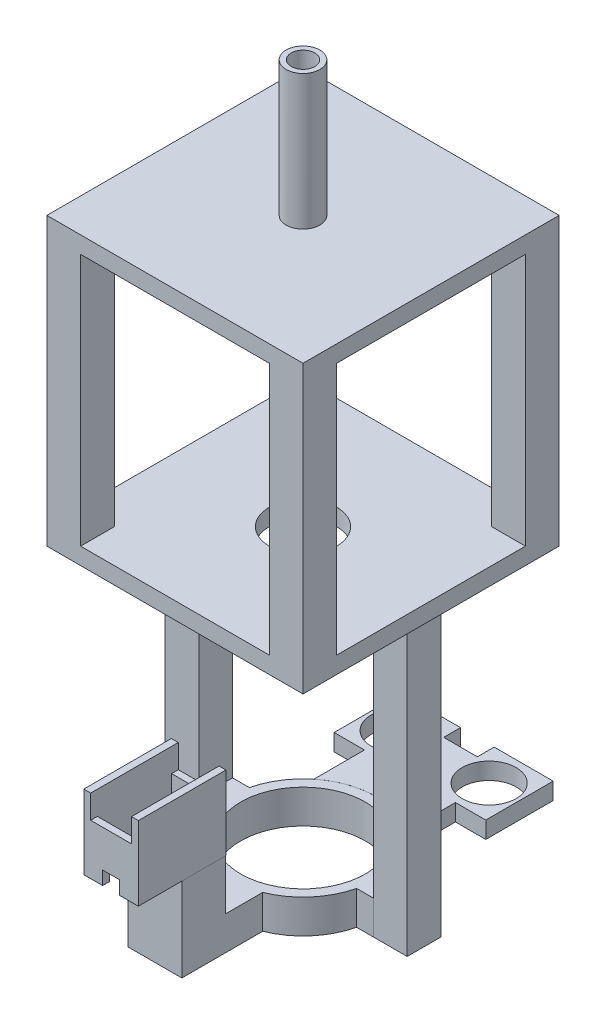
SolidWorks part; units mm, degrees
ref_plane "Front Plane" through (0, 0, 0) normal (0, 0, 1) x (1, 0, 0)
ref_plane "Top Plane" through (0, 0, 0) normal (0, 1, 0) x (1, 0, 0)
ref_plane "Right Plane" through (0, 0, 0) normal (1, 0, 0) x (0, 0, -1)
sketch "Sketch2" plane through (0, 0, 0) normal (0, 1, 0) x (1, 0, 0)
  line L0 (0, 18.5) -> (0, -18.5) construction
  line L1 (-18.5, 0) -> (18.5, 0) construction
  line L2 (0, -5) -> (0, 5) construction
  line L3 (-20.9105, 5) -> (-35.9105, 5)
  line L4 (-35.9105, 5) -> (-35.9105, -5)
  line L5 (-35.9105, -5) -> (-20.9105, -5)
  line L6 (35.9105, -5) -> (20.9105, -5)
  line L7 (35.9105, 5) -> (35.9105, -5)
  line L8 (20.9105, 5) -> (35.9105, 5)
  line L9 (0, 31.7332) -> (22.5, 31.7332)
  line L10 (22.5, 31.7332) -> (22.5, 51.7332)
  line L11 (22.5, 51.7332) -> (5, 51.7332)
  line L12 (-22.5, 51.7332) -> (-22.5, 31.7332)
  line L13 (-22.5, 31.7332) -> (0, 31.7332)
  line L14 (22.5, 41.7332) -> (21.5, 41.7332) construction
  line L20 (-5, 51.7332) -> (-22.5, 51.7332)
  line L21 (0, 46.7332) -> (0, 31.7332) construction
  line L22 (-5, 51.7332) -> (-5, 46.7332)
  line L23 (-5, 46.7332) -> (5, 46.7332)
  line L24 (5, 46.7332) -> (5, 51.7332)
  line L25 (13.5, 49.7332) -> (13.5, 51.7332) construction
  line L26 (13.5, 33.7332) -> (13.5, 31.7332) construction
  line L27 (-13.5, 41.7332) -> (13.5, 41.7332) construction
  line L28 (-13.5, 16.7332) -> (-13.5, 31.7332)
  line L29 (13.5, 31.7332) -> (13.5, 16.7332)
  line L30 (-8, -21.5) -> (8, -21.5) construction
  line L31 (-8, -19.9562) -> (-8, -43.9562)
  line L32 (-8, -43.9562) -> (8, -43.9562)
  line L33 (8, -43.9562) -> (8, -19.9562)
  line L34 (-20.9105, 5) -> (-25.9105, 5) construction
  line L35 (-5.5, -21.5) -> (5.5, -21.5) construction
  line L36 (-25.9105, 5) -> (-25.9105, -5)
  line L37 (25.9105, 5) -> (25.9105, -5)
  circle A0 centre (0, 0) radius 18.5
  circle A1 centre (0, 0) radius 21.5
  circle A2 centre (13.5, 41.7332) radius 8
  circle A3 centre (-13.5, 41.7332) radius 8
  point P9 (0, 0)
  point P45 (0, -21.5)
  point P54 (0, -21.5)
  dimension "D1" = 37
  dimension "D2" = 5
  dimension "D4" = 43
  dimension "D8" = 1
  dimension "D9" = 16
  dimension "D3" = 10
  dimension "D5" = 5
  dimension "D6" = 20
  dimension "D7" = 45
  dimension "D10" = 17.5
  dimension "D11" = 15
  dimension "D12" = 27
  dimension "D13" = 15
  dimension "D14" = 16
  dimension "D15" = 24
  dimension "D16" = 5
extrude "Connector sleeve" add sketch "Sketch2" along normal blind 5 and the other way blind 5 contours A1 A0 | A1 A0 | A1 A0 | A1 A0 region at (-17.6638, 0, -11.1562)
ref_plane "Plane2" through (0, 30, 0) normal (0, 1, 0) x (1, 0, 0)
extrude "Sensor holder" add sketch "Sketch2<10>" along normal blind 5 separate body contours L24 L23 L22 L20 L12 L13 L9 L10 L11 A2 A3 | A1 L29 L9 L13 L28 region at (0, 0, -25.7784) region at (0, 0, -40.8959)
sketch "Sketch2<10>" plane through (0, 0, 0) normal (0, 1, 0) x (1, 0, 0) same geometry as "Sketch2"
extrude "Arms" add sketch "Sketch2<18>" along normal blind 85 from offset 5 contours L36 L3 L4 L5 | L8 L37 L6 L7 region at (-30.9105, 0, 0) region at (30.9105, 0, 0) offset against normal yes
sketch "Sketch2<18>" plane through (0, 0, 0) normal (0, 1, 0) x (1, 0, 0) same geometry as "Sketch2"
extrude "Arms2" add sketch "Sketch2<22>" along normal blind 10 from offset 5 contours A1 L3 L4 L5 | A1 L6 L7 L8 | A1 L3 L36 L5 | A1 L6 L37 L8 region at (-23.6042, 0, 0) region at (-30.9105, 0, 0) region at (23.6042, 0, 0) region at (30.9105, 0, 0) offset against normal yes
sketch "Sketch2<22>" plane through (0, 0, 0) normal (0, 1, 0) x (1, 0, 0) same geometry as "Sketch2"
extrude "Servoholder" add sketch "Sketch2<21>" along normal blind 10 from offset 5 contours A1 L31 L32 L33 region at (0, 0, 32.4701) offset against normal yes
sketch "Sketch2<21>" plane through (0, 0, 0) normal (0, 1, 0) x (1, 0, 0) same geometry as "Sketch2"
sketch "Sketch31" plane through (0, 5, 0) normal (0, 1, 0) x (1, 0, 0)
  line L0 (-8, -43.9562) -> (-8, -30.9562)
  line L1 (-8, -19.9562) -> (-8, -43.9562) construction
  line L2 (-8, -30.9562) -> (8, -30.9562)
  line L3 (8, -43.9562) -> (8, -19.9562) construction
  line L4 (8, -30.9562) -> (8, -43.9562)
  line L5 (8, -43.9562) -> (-8, -43.9562)
  dimension "D1" = 13
extrude "Servoholder2" add sketch "Sketch31" along normal blind 15
sketch "Sketch33" plane through (0, 20, 0) normal (0, 1, 0) x (1, 0, 0)
  line L0 (0, -30.9562) -> (0, -32.9562) construction
  line L1 (8, -30.9562) -> (-8, -30.9562) construction
  line L2 (-8, -43.9562) -> (8, -43.9562) construction
  line L4 (8, -30.9562) -> (-8, -30.9562) construction
  line L6 (-8.1, -30.9562) -> (-8.1, -56.9562)
  line L7 (-8.1, -56.9562) -> (8.1, -56.9562)
  line L8 (8.1, -56.9562) -> (8.1, -30.9562)
  line L9 (0, -43.9562) -> (6.05, -43.9562) construction
  line L10 (0, -56.9562) -> (0, -54.9562) construction
  line L11 (-6.05, -54.9562) -> (6.05, -54.9562)
  line L12 (6.05, -54.9562) -> (6.05, -32.9562)
  line L13 (6.05, -32.9562) -> (-6.05, -32.9562)
  line L14 (-6.05, -54.9562) -> (-6.05, -32.9562)
  line L15 (-8.1, -30.9562) -> (8.1, -30.9562)
  dimension "D1" = 8.1
  dimension "D2" = 26
  dimension "D3" = 6.05
  dimension "D4" = 2
  dimension "D5" = 2
extrude "Servoholder3" add sketch "Sketch33" along normal blind 22
sketch "Servoholder4" plane through (0, 42, 0) normal (0, 1, 0) x (1, 0, 0)
  line L0 (-6.05, -32.9562) -> (-6.05, -30.9562)
  line L1 (8, -30.9562) -> (-8, -30.9562) construction
  line L2 (-6.05, -30.9562) -> (6.05, -30.9562)
  line L3 (8.1, -30.9562) -> (-8.1, -30.9562) construction
  line L4 (6.05, -30.9562) -> (6.05, -32.9562)
  line L5 (6.05, -32.9562) -> (-6.05, -32.9562)
  line L6 (-6.05, -43.9562) -> (6.05, -43.9562) construction
  line L7 (-6.05, -32.9562) -> (-6.05, -54.9562) construction
  line L8 (6.05, -54.9562) -> (6.05, -32.9562) construction
  line L9 (6.05, -56.9562) -> (6.05, -54.9562)
  line L10 (-6.05, -54.9562) -> (-6.05, -56.9562)
  line L11 (-6.05, -56.9562) -> (6.05, -56.9562)
  line L12 (6.05, -54.9562) -> (-6.05, -54.9562)
extrude "Servogrooves" cut sketch "Servoholder4" against normal blind 7
sketch "Sketch36" plane through (0, 0, 56.9562) normal (0, 0, 1) x (1, 0, 0)
  line L0 (0, 20) -> (0, 24) construction
  line L1 (-8.1, 20) -> (8.1, 20) construction
  line L2 (-2.5, 24) -> (2.5, 24)
  line L3 (-2.5, 24) -> (-2.5, 20)
  line L4 (-6.05, 20) -> (6.05, 20) construction
  line L5 (2.5, 24) -> (2.5, 20)
  line L6 (2.5, 20) -> (-2.5, 20)
  point P8 (0, 24)
  dimension "D1" = 4
  dimension "D2" = 2.5
extrude "Servowiring" cut sketch "Sketch36" against normal blind 2
sketch "Sketch4" plane through (0, 80, 0) normal (0, 1, 0) x (1, 0, 0)
  line L1 (-38, -38) -> (38, -38)
  line L2 (-38, -38) -> (-38, 38)
  line L3 (-38, 38) -> (38, 38)
  line L4 (38, -38) -> (38, 38)
  line L5 (-38, -38) -> (38, 38) construction
  line L6 (-38, 38) -> (38, -38) construction
  circle A0 centre (0, 0) radius 10
  point P0 (0, 0)
  dimension "D2" = 20
  dimension "D1" = 76
extrude "Motor enclosure" add sketch "Sketch4" along normal blind 5
sketch "Sketch6" plane through (0, 85, 0) normal (0, 1, 0) x (1, 0, 0)
  line L0 (-38, 38) -> (-28, 38)
  line L1 (38, 38) -> (-38, 38) construction
  line L2 (-28, 38) -> (-28, 28)
  line L3 (-28, 28) -> (-38, 28)
  line L4 (-38, 38) -> (-38, -38) construction
  line L5 (-38, 28) -> (-38, 38)
  line L6 (0, 38) -> (0, -38) construction
  line L7 (-38, -38) -> (38, -38) construction
  line L8 (-38, 0) -> (38, 0) construction
  line L9 (38, -38) -> (38, 38) construction
  line L10 (28, 28) -> (38, 28)
  line L11 (38, 28) -> (38, 38)
  line L12 (38, 38) -> (28, 38)
  line L13 (28, 38) -> (28, 28)
  line L14 (28, -28) -> (38, -28)
  line L15 (38, -28) -> (38, -38)
  line L16 (38, -38) -> (28, -38)
  line L17 (28, -38) -> (28, -28)
  line L18 (-28, -28) -> (-38, -28)
  line L19 (-28, -38) -> (-28, -28)
  line L20 (-38, -28) -> (-38, -38)
  line L21 (-38, -38) -> (-28, -38)
  dimension "D2" = 10
extrude "Motor enclosure 2" add sketch "Sketch6" along normal blind 75
sketch "Sketch7" plane through (0, 160, 0) normal (0, 1, 0) x (1, 0, 0)
  line L0 (-38, 38) -> (38, 38)
  line L1 (38, 38) -> (38, -38)
  line L2 (38, -38) -> (-38, -38)
  line L3 (-38, -28) -> (-38, -38) construction
  line L4 (-38, -38) -> (-38, 38)
extrude "Motor enclosure 3" add sketch "Sketch7" along normal blind 5 contours L1 L2 L4 L0
sketch "Sketch8" plane through (0, 165, 0) normal (0, 1, 0) x (1, 0, 0)
  circle A0 centre (0, 0) radius 5
  point P0 (0, 0)
  dimension "D1" = 10
extrude "Connector" add sketch "Sketch8" along normal blind 40
sketch "Sketch26" plane through (0, 205, 0) normal (0, 1, 0) x (1, 0, 0)
  circle A0 centre (0, 0) radius 3.5
  dimension "D1" = 7
extrude "Cut-Extrude1" cut sketch "Sketch26" against normal up to next (45 mm away)
